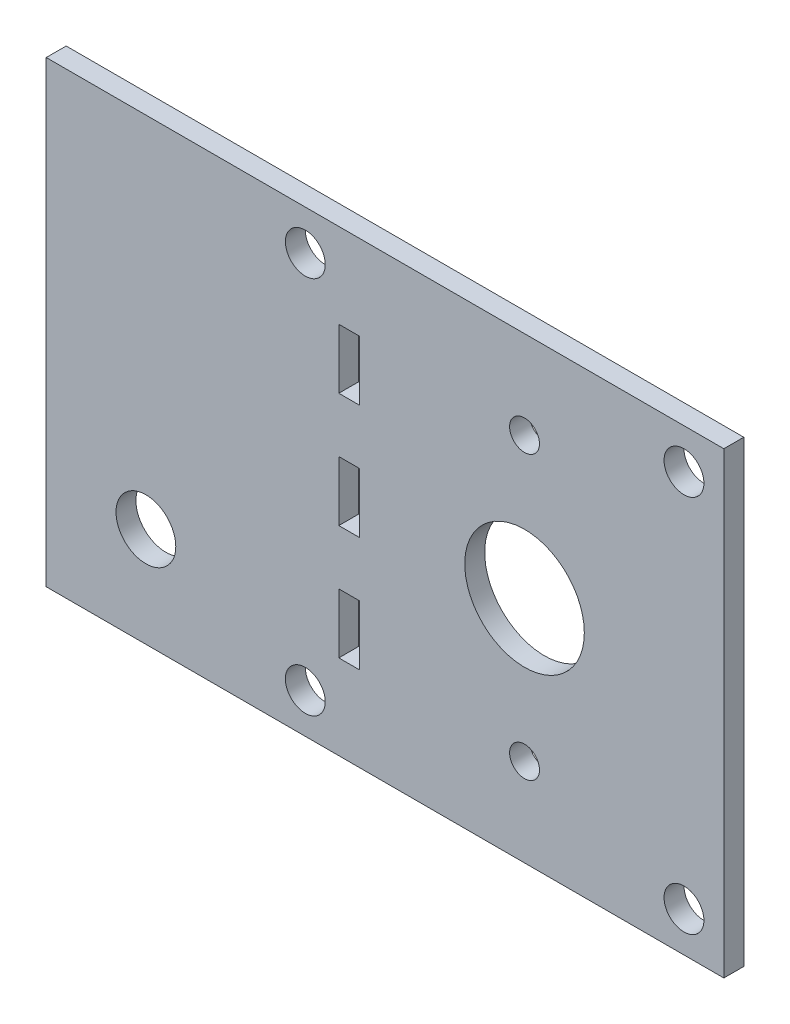
SolidWorks part; units mm, degrees
ref_plane "Front Plane" through (0, 0, 0) normal (0, 0, 1) x (1, 0, 0)
ref_plane "Top Plane" through (0, 0, 0) normal (0, 1, 0) x (1, 0, 0)
ref_plane "Right Plane" through (0, 0, 0) normal (1, 0, 0) x (0, 0, -1)
sketch "Sketch1" plane through (0, 0, 0) normal (0, 0, 1) x (1, 0, 0)
  line L0 (0, 73.025) -> (0, -73.025) construction
  line L1 (63.5, 73.025) -> (-152.4, 73.025)
  line L2 (63.5, 73.025) -> (63.5, -73.025)
  line L3 (63.5, -73.025) -> (-152.4, -73.025)
  line L4 (-152.4, 73.025) -> (-152.4, -73.025)
  line L5 (0, 45) -> (0, -45) construction
  line L6 (-55.88, 73.025) -> (-55.88, 36.5125) construction
  line L7 (-59.182, -9.525) -> (-52.578, -9.525)
  line L8 (-59.182, -9.525) -> (-59.182, 9.525)
  line L9 (-59.182, 9.525) -> (-52.578, 9.525)
  line L10 (-52.578, -9.525) -> (-52.578, 9.525)
  line L11 (-59.182, -9.525) -> (-52.578, 9.525) construction
  line L12 (-59.182, 9.525) -> (-52.578, -9.525) construction
  line L13 (-59.182, 46.0375) -> (-52.578, 46.0375)
  line L14 (-59.182, 46.0375) -> (-59.182, 26.9875)
  line L15 (-59.182, 26.9875) -> (-52.578, 26.9875)
  line L16 (-52.578, 46.0375) -> (-52.578, 26.9875)
  line L17 (-59.182, 46.0375) -> (-52.578, 26.9875) construction
  line L18 (-59.182, 26.9875) -> (-52.578, 46.0375) construction
  line L19 (-59.182, -26.9875) -> (-52.578, -26.9875)
  line L20 (-59.182, -26.9875) -> (-59.182, -46.0375)
  line L21 (-59.182, -46.0375) -> (-52.578, -46.0375)
  line L22 (-52.578, -26.9875) -> (-52.578, -46.0375)
  line L23 (-59.182, -26.9875) -> (-52.578, -46.0375) construction
  line L24 (-59.182, -46.0375) -> (-52.578, -26.9875) construction
  line L25 (-55.88, 36.5125) -> (-55.88, 0) construction
  line L26 (-55.88, 0) -> (-55.88, -36.5125) construction
  line L27 (-55.88, -36.5125) -> (-55.88, -73.025) construction
  circle A0 centre (50.8, 60.325) radius 6.35
  circle A1 centre (50.8, -60.325) radius 6.35
  circle A2 centre (0, 0) radius 19.05
  circle A3 centre (0, 45) radius 4.7625
  circle A4 centre (0, -45) radius 4.7625
  circle A5 centre (-69.85, 60.325) radius 6.35
  circle A6 centre (-69.85, -60.325) radius 6.35
  point P0 (0, 0)
  point P14 (0, 0)
  point P19 (0, 0)
  point P24 (-55.88, 36.5125)
  point P28 (-55.88, 0)
  point P34 (-55.88, -36.5125)
  dimension "D2" = 12.7
  dimension "D6" = 38.1
  dimension "D8" = 9.525
  dimension "D1" = 146.05
  dimension "D3" = 12.7
  dimension "D4" = 12.7
  dimension "D5" = 50.8
  dimension "D7" = 90
  dimension "D9" = 12.7
  dimension "D10" = 152.4
  dimension "D11" = 69.85
  dimension "D12" = 19.05
  dimension "D13" = 6.604
  dimension "D14" = 55.88
extrude "Boss-Extrude1" add sketch "Sketch1" along normal mid plane 6.35
sketch "Sketch2" plane through (0, 0, 3.175) normal (0, 0, 1) x (1, 0, 0)
  line L0 (-152.4, -73.025) -> (63.5, -73.025) construction
  line L1 (-152.4, 73.025) -> (-152.4, -73.025) construction
  circle A0 centre (-120.65, -41.275) radius 9.525
  dimension "D1" = 19.05
  dimension "D2" = 31.75
  dimension "D3" = 31.75
extrude "Cut-Extrude1" cut sketch "Sketch2" against normal through all
